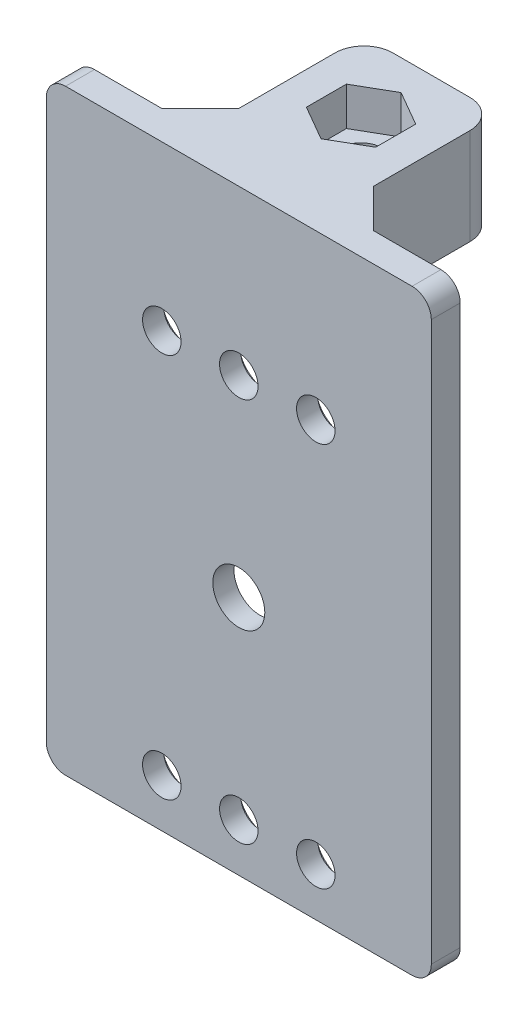
SolidWorks part; units mm, degrees
ref_plane "前视基准面" through (0, 0, 0) normal (0, 0, 1) x (1, 0, 0)
ref_plane "上视基准面" through (0, 0, 0) normal (0, 1, 0) x (1, 0, 0)
ref_plane "右视基准面" through (0, 0, 0) normal (1, 0, 0) x (0, 0, -1)
sketch "草图1" plane through (0, 0, 0) normal (0, 0, 1) x (1, 0, 0)
  line L0 (0, -1000) -> (0, 49000) construction
  line L1 (-15, -37) -> (15, -37) construction
  line L2 (-15, -37) -> (-15, 37)
  line L3 (-15, 37) -> (15, 37)
  line L4 (15, -37) -> (15, 37)
  line L5 (-15, -37) -> (15, 37) construction
  line L6 (-15, 37) -> (15, -37) construction
  line L7 (-15, -25) -> (15, -25)
  line L8 (15, -25) -> (20, -25)
  line L9 (20, -25) -> (20, 37)
  line L10 (20, 37) -> (15, 37)
  line L11 (-15, 37) -> (-20, 37)
  line L12 (-20, 37) -> (-20, -25)
  line L13 (-20, -25) -> (-15, -25)
  line L14 (-15, -25) -> (15, -25) construction
  line L15 (-15, -25) -> (-15, 25)
  line L16 (-15, 25) -> (15, 25) construction
  line L17 (15, -25) -> (15, 25)
  line L18 (-15, -25) -> (15, 25) construction
  line L19 (-15, 25) -> (15, -25) construction
  line L20 (-15, 0) -> (15, 0) construction
  circle A0 centre (0, 20) radius 2
  circle A1 centre (8, 20) radius 2
  circle A2 centre (-8, 20) radius 2
  circle A3 centre (0, 0) radius 2.7
  circle A4 centre (8, -20) radius 2
  circle A5 centre (0, -20) radius 2
  circle A6 centre (-8, -20) radius 2
  point P0 (0, 0)
  point P19 (0, 0)
  dimension "D5" = 4
  dimension "D7" = 4
  dimension "D3" = 5.4
  dimension "D1" = 30
  dimension "D2" = 12
  dimension "D4" = 20
  dimension "D6" = 16
  dimension "D8" = 5
  dimension "D9" = 5
  dimension "D12" = 40
extrude "凸台-拉伸1" add sketch "草图1" along normal blind 3 contours L3 | L3 L2 L1 L4 | L9 L10 L4 L8 | L12 L13 L2 L11 region at (-17.5, 6, 0) region at (0, 6.3348, 0) region at (17.5, 6, 0)
sketch "草图3" plane through (0, 0, 0) normal (0, 0, -1) x (-1, 0, 0)
  line L0 (20, 37) -> (-20, 37) construction
  line L1 (-7, 27) -> (7, 27)
  line L2 (-7, 27) -> (-7, 37)
  line L3 (-7, 37) -> (7, 37)
  line L4 (7, 27) -> (7, 37)
  line L5 (-7, 27) -> (7, 37) construction
  line L6 (-7, 37) -> (7, 27) construction
  point P0 (0, 32)
  dimension "D1" = 14
  dimension "D2" = 10
extrude "凸台-拉伸2" add sketch "草图3" along normal blind 17
sketch "草图5" plane through (0, 27, 0) normal (0, -1, 0) x (1, 0, 0)
  line L0 (-7, -17) -> (-7, 0) construction
  line L1 (3.6, -11.7785) -> (3.6, -7.6215)
  line L2 (3.6, -7.6215) -> (0, -5.5431)
  line L3 (0, -5.5431) -> (-3.6, -7.6215)
  line L4 (-3.6, -7.6215) -> (-3.6, -11.7785)
  line L5 (-3.6, -11.7785) -> (0, -13.8569)
  line L6 (0, -13.8569) -> (3.6, -11.7785)
  line L7 (7, -17) -> (-7, -17) construction
  line L8 (-7, -17) -> (-7, 0) construction
  line L9 (7, 0) -> (-7, 0) construction
  circle A0 centre (0, -9.7) radius 3.6 construction
  point P16 (0, 0)
  dimension "D1" = 7.2
  dimension "D2" = 7.3
  dimension "D3" = 9.7
extrude "切除-拉伸1" cut sketch "草图5" along normal blind 4 from surface starting at face at (-1.625, 37, -5.625)
sketch "草图6" plane through (0, 33, 0) normal (0, 1, 0) x (-1, 0, 0)
  line L1 (0, -5.5431) -> (-3.6, -7.6215) construction
  line L2 (-3.6, -7.6215) -> (-3.6, -11.7785) construction
  line L3 (-3.6, -11.7785) -> (0, -13.8569) construction
  line L4 (0, -13.8569) -> (3.6, -11.7785) construction
  line L5 (3.6, -11.7785) -> (3.6, -7.6215) construction
  line L6 (3.6, -7.6215) -> (0, -5.5431) construction
  circle A0 centre (0, -9.7) radius 2.2
  circle A1 centre (0, -9.7) radius 3.6 construction
  dimension "D1" = 4.4
  dimension "D2" = 9.7
extrude "切除-拉伸2" cut sketch "草图6" against normal up to next
fillet "圆角1" radius 3 2 edges at (-7, 32, -17) (7, 32, -17)
chamfer "倒角1" distance 4 angle 45 2 edges
extrude "切除-拉伸3" cut sketch "草图5<2>" against normal blind 3
sketch "草图5<2>" plane through (0, 27, 0) normal (0, -1, 0) x (1, 0, 0) same geometry as "草图5"
fillet "圆角2" radius 2 4 edges at (-20, 37, 1.5) (20, 37, 1.5) (20, -25, 1.5) (-20, -25, 1.5)
sketch "草图7" plane through (0, 0, 0) normal (0, 0, -1) x (-1, 0, 0)
  line L0 (-1000, 0) -> (49000, 0) construction
  line L1 (0, -1000) -> (0, 49000) construction
  circle A0 centre (0, 0) radius 5
  circle A1 centre (-8, 20) radius 3
  circle A2 centre (0, 20) radius 3
  circle A3 centre (8, 20) radius 3
  circle A4 centre (8, -20) radius 3
  circle A5 centre (0, -20) radius 3
  circle A6 centre (-8, -20) radius 3
  dimension "D1" = 6
  dimension "D2" = 6
  dimension "D3" = 10
extrude "切除-拉伸4" cut sketch "草图7" against normal blind 0.8
